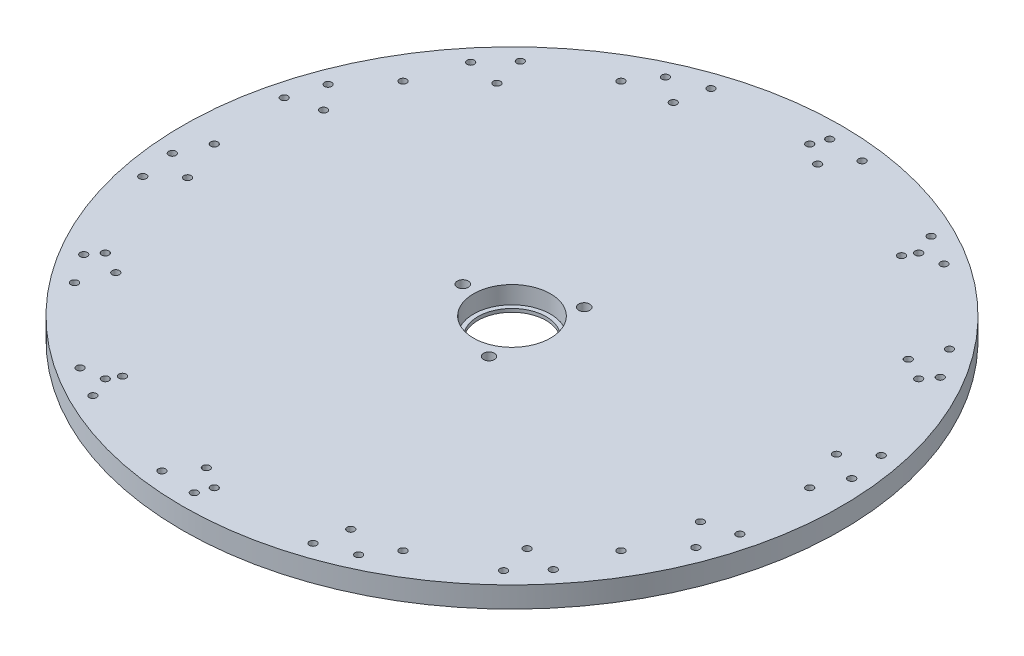
SolidWorks part; units mm, degrees
ref_plane "Front Plane" through (0, 0, 0) normal (0, 0, 1) x (1, 0, 0)
ref_plane "Top Plane" through (0, 0, 0) normal (0, 1, 0) x (1, 0, 0)
ref_plane "Right Plane" through (0, 0, 0) normal (1, 0, 0) x (0, 0, -1)
sketch "Sketch1" plane through (0, 0, 0) normal (0, 1, 0) x (1, 0, 0)
  circle A0 centre (0, 0) radius 150
extrude "Boss-Extrude1" add sketch "Sketch1" along normal blind 9.52
sketch "Sketch2" plane through (0, 9.52, 0) normal (0, 1, 0) x (1, 0, 0)
  circle A0 centre (0, 0) radius 15.5
extrude "Cut-Extrude1" cut sketch "Sketch2" against normal through all
sketch "Sketch3" plane through (0, 9.52, 0) normal (0, 1, 0) x (1, 0, 0)
  circle A0 centre (0, 0) radius 17.505
extrude "Cut-Extrude2" cut sketch "Sketch3" against normal blind 8
sketch "Sketch4" plane through (0, 9.52, 0) normal (0, 1, 0) x (1, 0, 0)
  circle A0 centre (10.7251, -21.1932) radius 2.5
  circle A1 centre (-23.7164, 1.3084) radius 2.5
  circle A2 centre (12.9913, 19.8849) radius 2.5
  circle A3 centre (67.75, -117.3464) radius 1.65
  circle A4 centre (0, -135.5) radius 1.65
  circle A5 centre (-67.75, -117.3464) radius 1.65
  circle A6 centre (-117.3464, -67.75) radius 1.65
  circle A7 centre (-135.5, 0) radius 1.65
  circle A8 centre (-117.3464, 67.75) radius 1.65
  circle A9 centre (-67.75, 117.3464) radius 1.65
  circle A10 centre (0, 135.5) radius 1.65
  circle A11 centre (67.75, 117.3464) radius 1.65
  circle A12 centre (117.3464, 67.75) radius 1.65
  circle A13 centre (135.5, 0) radius 1.65
  circle A14 centre (117.3464, -67.75) radius 1.65
extrude "Cut-Extrude3" cut sketch "Sketch4" against normal through all
sketch "Sketch6" plane through (0, 0, 0) normal (0, -1, 0) x (-1, 0, 0)
  circle A0 centre (-63.9648, 126.7902) radius 1.65
  circle A1 centre (-77.8212, 118.7902) radius 1.65
  circle A2 centre (-64.893, 112.3979) radius 1.65
  circle A3 centre (-9.6989, 129.423) radius 1.65
  circle A4 centre (-2.618, 141.9873) radius 1.65
  circle A5 centre (-18.5733, 140.7916) radius 1.65
  circle A6 centre (59.2472, 129.0621) radius 1.65
  circle A7 centre (44.3532, 134.9075) radius 1.65
  circle A8 centre (47.4161, 120.8143) radius 1.65
  circle A9 centre (109.3778, 90.5745) radius 1.65
  circle A10 centre (98.4951, 102.3033) radius 1.65
  circle A11 centre (95.1398, 88.2769) radius 1.65
  circle A12 centre (133.1287, 49.4367) radius 1.65
  circle A13 centre (124.0199, 38.2551) radius 1.65
  circle A14 centre (137.8448, 34.1476) radius 1.65
  circle A15 centre (141.3946, -13.2214) radius 1.65
  circle A16 centre (128.3363, -19.3436) radius 1.65
  circle A17 centre (139.01, -29.0427) radius 1.65
  circle A18 centre (121.6556, -73.2609) radius 1.65
  circle A19 centre (112.6425, -86.4808) radius 1.65
  circle A20 centre (107.2342, -73.111) radius 1.65
  circle A21 centre (64.893, -112.3979) radius 1.65
  circle A22 centre (63.9648, -126.7902) radius 1.65
  circle A23 centre (77.8212, -118.7902) radius 1.65
  circle A24 centre (9.6989, -129.423) radius 1.65
  circle A25 centre (2.618, -141.9873) radius 1.65
  circle A26 centre (18.5733, -140.7916) radius 1.65
  circle A27 centre (-44.3532, -134.9075) radius 1.65
  circle A28 centre (-59.2472, -129.0621) radius 1.65
  circle A29 centre (-47.4161, -120.8143) radius 1.65
  circle A30 centre (-98.4951, -102.3033) radius 1.65
  circle A31 centre (-109.3778, -90.5745) radius 1.65
  circle A32 centre (-95.1398, -88.2769) radius 1.65
  circle A33 centre (-124.0199, -38.2551) radius 1.65
  circle A34 centre (-137.8448, -34.1476) radius 1.65
  circle A35 centre (-133.1287, -49.4367) radius 1.65
  circle A36 centre (-128.3363, 19.3436) radius 1.65
  circle A37 centre (-141.3946, 13.2214) radius 1.65
  circle A38 centre (-139.01, 29.0427) radius 1.65
  circle A39 centre (-107.2342, 73.111) radius 1.65
  circle A40 centre (-121.6556, 73.2609) radius 1.65
  circle A41 centre (-112.6425, 86.4808) radius 1.65
extrude "Cut-Extrude5" cut sketch "Sketch6" against normal through all
